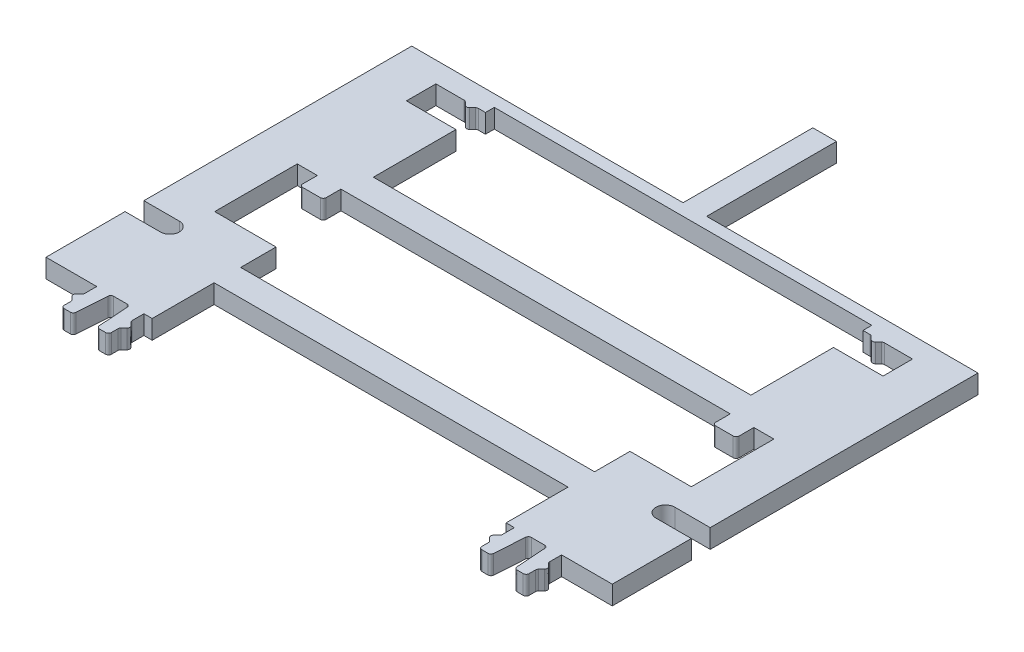
SolidWorks part; units mm, degrees
ref_plane "Front Plane" through (0, 0, 0) normal (0, 0, 1) x (1, 0, 0)
ref_plane "Top Plane" through (0, 0, 0) normal (0, 1, 0) x (1, 0, 0)
ref_plane "Right Plane" through (0, 0, 0) normal (1, 0, 0) x (0, 0, -1)
sketch "Sketch1" plane through (0, 0, 0) normal (0, 1, 0) x (1, 0, 0)
  line L0 (-68.9296, 0) -> (-64.6296, 0)
  line L1 (-59.9296, 0) -> (-59.9296, 5.25)
  line L2 (-61.4296, 17.5) -> (-61.4296, 16.25)
  line L3 (-65.1296, 10.5) -> (-65.1296, 17.5)
  line L4 (-65.1296, 17.5) -> (-63.4296, 17.5)
  line L5 (-64.6296, 0) -> (-64.6296, -0.9964)
  line L6 (-64.3796, -3) -> (-63.8635, -3)
  line L7 (-59.9296, 7.5) -> (-44.9296, 7.5)
  line L8 (-44.9296, 19.75) -> (-60.9296, 19.75)
  line L9 (-60.9296, 19.75) -> (-60.9296, 26.75)
  line L10 (-60.9296, 29.25) -> (-60.9296, 30)
  line L11 (-63.1957, 0) -> (-62.0635, 0)
  line L12 (-68.9296, 0) -> (-68.9296, 6.7)
  line L13 (-68.9296, 31) -> (-45.9296, 31)
  line L14 (-44.9296, 42) -> (-44.9296, 0) construction
  line L15 (-44.9296, 42) -> (-44.9296, 30)
  line L16 (-63.614, -2.7666) -> (-63.4451, -0.2334)
  line L17 (-61.3957, -3) -> (-60.8796, -3)
  line L18 (-61.814, -0.2334) -> (-61.6451, -2.7666)
  line L19 (-60.9296, 26.75) -> (-65.1296, 26.75)
  line L20 (-64.7028, -1.1732) -> (-64.9528, -1.4232)
  line L21 (-64.9528, -1.7768) -> (-64.7028, -2.0268)
  line L22 (-64.6296, -2.2036) -> (-64.6296, -2.75)
  line L23 (-60.6296, 0) -> (-60.6296, -0.9964)
  line L24 (-60.5564, -1.1732) -> (-60.3064, -1.4232)
  line L25 (-60.3064, -1.7768) -> (-60.5564, -2.0268)
  line L26 (-60.6296, -2.2036) -> (-60.6296, -2.75)
  line L27 (-65.1296, 10.5) -> (-59.9296, 10.5)
  line L28 (-61.6796, 16) -> (-63.1796, 16)
  line L29 (-63.4296, 16.25) -> (-63.4296, 17.5)
  line L30 (-44.9296, 19.75) -> (-44.9296, 17.5)
  line L31 (-44.9296, 5.25) -> (-59.9296, 5.25)
  line L32 (-60.6296, 0) -> (-59.9296, 0)
  line L33 (-59.9296, 7.5) -> (-59.9296, 10.5)
  line L34 (-61.4296, 17.5) -> (-44.9296, 17.5)
  line L35 (-65.9296, 8.3) -> (-68.9296, 8.3)
  line L36 (-65.1296, 26.75) -> (-65.1296, 29.25)
  line L37 (-65.1296, 29.25) -> (-62.7331, 29.25)
  line L38 (-60.9296, 30) -> (-44.9296, 30)
  line L39 (-62.5564, 29.1768) -> (-62.3064, 28.9268)
  line L40 (-61.9528, 28.9268) -> (-61.7028, 29.1768)
  line L41 (-61.526, 29.25) -> (-60.9296, 29.25)
  line L42 (-65.9296, 6.7) -> (-68.9296, 6.7)
  line L43 (-68.9296, 8.3) -> (-68.9296, 20)
  line L44 (-44.9296, 7.5) -> (-44.9296, 5.25)
  line L55 (-45.9296, 31) -> (-45.9296, 42)
  line L56 (-45.9296, 42) -> (-44.9296, 42)
  line L61 (-68.9296, 20) -> (-68.9296, 31)
  arc A1 (-61.526, 29.25) -> (-61.7028, 29.1768) centre (-61.526, 29) ccw
  arc A2 (-61.9528, 28.9268) -> (-62.3064, 28.9268) centre (-62.1296, 29.1036) cw
  arc A3 (-62.5564, 29.1768) -> (-62.7331, 29.25) centre (-62.7331, 29) ccw
  arc A4 (-60.6296, -0.9964) -> (-60.5564, -1.1732) centre (-60.3796, -0.9964) ccw
  arc A5 (-60.3064, -1.4232) -> (-60.3064, -1.7768) centre (-60.4831, -1.6) cw
  arc A6 (-60.5564, -2.0268) -> (-60.6296, -2.2036) centre (-60.3796, -2.2036) ccw
  arc A7 (-60.6296, -2.75) -> (-60.8796, -3) centre (-60.8796, -2.75) cw
  arc A8 (-61.3957, -3) -> (-61.6451, -2.7666) centre (-61.3957, -2.75) cw
  arc A9 (-61.814, -0.2334) -> (-62.0635, 0) centre (-62.0635, -0.25) ccw
  arc A10 (-63.1957, 0) -> (-63.4451, -0.2334) centre (-63.1957, -0.25) ccw
  arc A11 (-63.614, -2.7666) -> (-63.8635, -3) centre (-63.8635, -2.75) cw
  arc A12 (-64.3796, -3) -> (-64.6296, -2.75) centre (-64.3796, -2.75) cw
  arc A13 (-64.6296, -2.2036) -> (-64.7028, -2.0268) centre (-64.8796, -2.2036) ccw
  arc A14 (-64.9528, -1.7768) -> (-64.9528, -1.4232) centre (-64.776, -1.6) cw
  arc A15 (-64.7028, -1.1732) -> (-64.6296, -0.9964) centre (-64.8796, -0.9964) ccw
  arc A16 (-61.4296, 16.25) -> (-61.6796, 16) centre (-61.6796, 16.25) cw
  arc A17 (-63.1796, 16) -> (-63.4296, 16.25) centre (-63.1796, 16.25) cw
  arc A19 (-65.9296, 6.7) -> (-65.9296, 8.3) centre (-65.9296, 7.5) ccw
  point P25 (-61.6296, 29.25)
  point P30 (-62.1296, 28.75)
  point P47 (-62.6296, 29.25)
  point P54 (-60.6296, -1.1)
  point P57 (-60.1296, -1.6)
  point P62 (-60.6296, -3)
  point P66 (-61.6296, -3)
  point P74 (-61.8296, 0)
  point P77 (-63.4296, 0)
  point P80 (-63.6296, -3)
  point P83 (-64.6296, -3)
  point P86 (-64.6296, -2.1)
  point P89 (-65.1296, -1.6)
  point P92 (-64.6296, -1.1)
  point P96 (-61.4296, 16)
  point P99 (-63.4296, 16)
  dimension "D13" = 0.25
  dimension "D42" = 0.25
  dimension "D44" = 0.25
  dimension "D49" = 3
  dimension "D51" = 0.8
  dimension "D4" = 1.6
  dimension "D6" = 3
  dimension "D7" = 15
  dimension "D8" = 7
  dimension "D9" = 24
  dimension "D10" = 20.2
  dimension "D11" = 16
  dimension "D12" = 10.5
  dimension "D14" = 1
  dimension "D18" = 3
  dimension "D19" = 0.75
  dimension "D20" = 7
  dimension "D22" = 1
  dimension "D23" = 0.5
  dimension "D24" = 0.5
  dimension "D25" = 0.5
  dimension "D28" = 2.5
  dimension "D29" = 1.5
  dimension "D30" = 11
  dimension "D31" = 1.2
  dimension "D32" = 1
  dimension "D33" = 1
  dimension "D34" = 1.2
  dimension "D35" = 4
  dimension "D36" = 0.5
  dimension "D37" = 0.5
  dimension "D38" = 0.5
  dimension "D39" = 1.6
  dimension "D40" = 0.5
  dimension "D41" = 0.5
  dimension "D43" = 2
  dimension "D47" = 31
  dimension "D48" = 2.25
  dimension "D50" = 3
other "AlignGroup1"
extrude "Boss-Extrude1" add sketch "Sketch1" along normal blind 1.6
mirror "Mirror1" about plane through (-44.9296, 1.6, -42) normal (-1, 0, 0) of "Boss-Extrude1"
